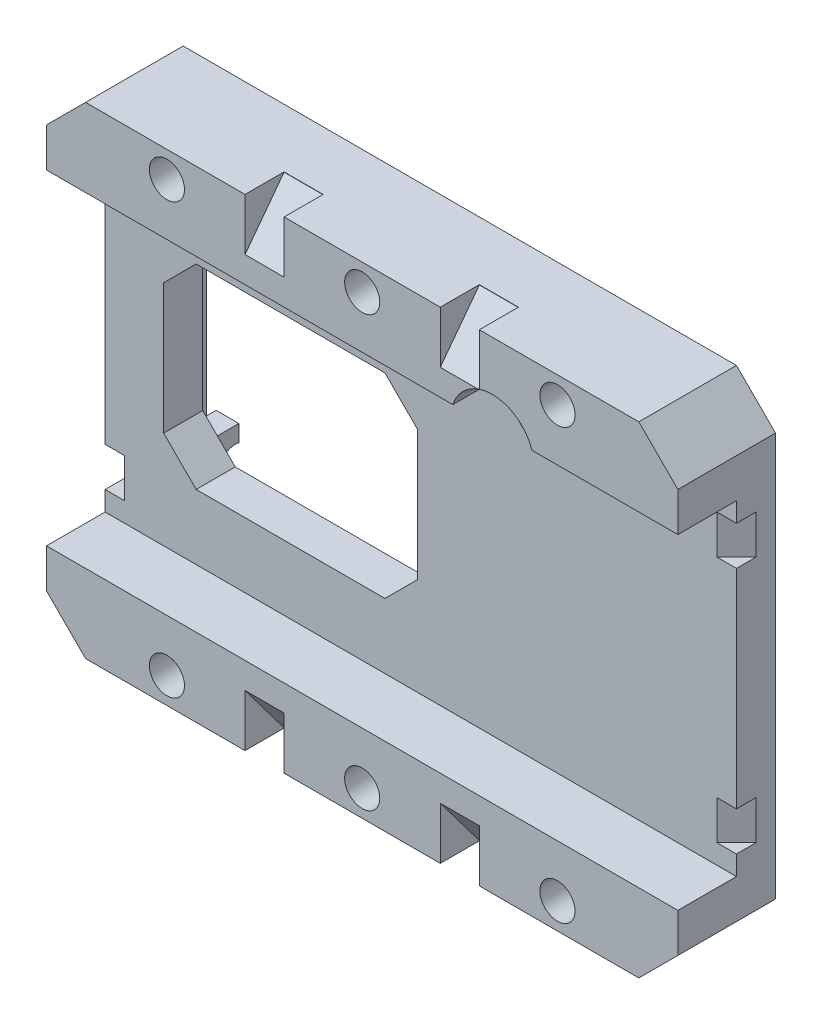
SolidWorks part; units mm, degrees
ref_plane "前视基准面" through (0, 0, 0) normal (0, 0, 1) x (1, 0, 0)
ref_plane "上视基准面" through (0, 0, 0) normal (0, 1, 0) x (1, 0, 0)
ref_plane "右视基准面" through (0, 0, 0) normal (1, 0, 0) x (0, 0, -1)
ref_plane "基准面4" through (0, 0, 5.028) normal (0, 0, -1) x (-1, 0, 0)
sketch "草图1" plane through (0, 0, 5.028) normal (0, 0, -1) x (-1, 0, 0)
  line L0 (-24.25, 18.5) -> (-24.25, -18.5)
  line L1 (-24.25, -18.5) -> (24.25, -18.5)
  line L2 (24.25, -18.5) -> (24.25, 18.5)
  line L3 (24.25, 18.5) -> (-24.25, 18.5)
  line L4 (-24.25, 0) -> (24.25, 0) construction
  line L5 (0, 18.5) -> (0, -18.5) construction
  point P8 (0, 0)
  point P9 (0, 0)
  dimension "D1" = 48.5
  dimension "D2" = 37
extrude "凸台-拉伸1" add sketch "草图1" against normal blind 7.5
sketch "草图2" plane through (24.25, 0, 0) normal (1, 0, 0) x (0, 0, -1)
  line L0 (-12.528, 12.5) -> (-12.528, -12.5)
  line L1 (-12.528, -12.5) -> (-8.028, -12.5)
  line L2 (-8.028, -12.5) -> (-8.028, 12.5)
  line L3 (-8.028, 12.5) -> (-12.528, 12.5)
extrude "切除-拉伸1" cut sketch "草图2" against normal through all
sketch "草图3" plane through (0, 0, 5.028) normal (0, 0, -1) x (-1, 0, 0)
  line L0 (21.75, 13.75) -> (21.75, -13.75)
  line L1 (21.75, -13.75) -> (-19.25, -13.75)
  line L2 (-19.25, -13.75) -> (-19.25, 13.75)
  line L3 (-19.25, 13.75) -> (21.75, 13.75)
  line L4 (-19.25, 0) -> (21.75, 0) construction
  line L5 (24.25, -18.5) -> (24.25, 18.5) construction
  line L6 (-24.25, 18.5) -> (-24.25, -18.5) construction
  point P4 (0, 0)
  point P8 (0, 0)
  point P9 (0, 0)
  dimension "D1" = 27.5
  dimension "D2" = 2.5
  dimension "D3" = 5
extrude "凸台-拉伸2" add sketch "草图3" along normal blind 3.028
sketch "草图4" plane through (0, 0, 2) normal (0, 0, -1) x (-1, 0, 0)
  line L0 (-18.25, -12.5) -> (20, -12.5)
  line L1 (20, -12.5) -> (20, 12.5)
  line L2 (20, 12.5) -> (-18.25, 12.5)
  line L3 (-18.25, 12.5) -> (-18.25, -12.5)
  line L5 (21.75, -13.75) -> (21.75, 13.75) construction
  line L6 (-19.25, 13.75) -> (-19.25, -13.75) construction
  line L7 (-19.25, -13.75) -> (21.75, -13.75) construction
  point P8 (0, 0)
  point P9 (0, 0)
  point P11 (0, 0)
  dimension "D1" = 1
  dimension "D2" = 1.25
  dimension "D3" = 1.75
extrude "切除-拉伸2" cut sketch "草图4" against normal blind 3.028
sketch "草图5" plane through (18.25, 0, 0) normal (-1, 0, 0) x (0, 0, 1)
  line L0 (2, 7.0344) -> (2, -7.0344)
  arc A0 (2, -7.0344) -> (2, 7.0344) centre (-7.722, 0) ccw
extrude "切除-拉伸3" cut sketch "草图5" against normal through all
sketch "草图6" plane through (-21.75, 0, 0) normal (-1, 0, 0) x (0, 0, 1)
  line L0 (2, 7.0344) -> (2, -7.0344)
  arc A0 (2, -7.0344) -> (2, 7.0344) centre (-7.722, 0) ccw
extrude "切除-拉伸4" cut sketch "草图6" against normal through all
sketch "草图7" plane through (0, 0, 8.028) normal (0, 0, 1) x (1, 0, 0)
  line L0 (-7.9784, 7.0292) -> (-13.0216, 7.0292)
  line L1 (-13.0216, -7.0292) -> (-7.9784, -7.0292)
  arc A0 (-1.5, 0) -> (-7.9784, 7.0292) centre (-7.9784, 0.5292) ccw
  arc A1 (-13.0216, 7.0292) -> (-19.5, 0) centre (-13.0216, 0.5292) ccw
  arc A2 (-19.5, 0) -> (-13.0216, -7.0292) centre (-13.0216, -0.5292) ccw
  arc A3 (-7.9784, -7.0292) -> (-1.5, 0) centre (-7.9784, -0.5292) ccw
  point P11 (0, 0)
  dimension "D1" = 19.5
  dimension "D2" = 18
extrude "切除-拉伸5" cut sketch "草图7" against normal through all
ref_plane "基准面5" through (0, 11.5, 0) normal (0, 1, 0) x (1, 0, 0)
sketch "草图8" plane through (0, 11.5, 0) normal (0, 1, 0) x (1, 0, 0)
  line L0 (13, -2.1) -> (10, -2.1)
  line L1 (10, -2.1) -> (10, -12.528)
  line L2 (10, -12.528) -> (13, -12.528)
  line L3 (13, -12.528) -> (13, -2.1)
  line L4 (10, -2.1) -> (10, -12.528) construction
hole_wizard "Ø2.5 (2.5) 直径孔1" positions "草图10" profile "草图9" hole size "Ø2.5" standard "ANSI Metric"
sketch "草图10" plane through (-21.75, 0, 0) normal (-1, 0, 0) x (0, 0, 1)
  point P0 (2.278, 10)
sketch "草图9" plane through (-21.75, 10, 2.278) normal (0, 1, 0) x (0, 0, 1)
  line L0 (0, 0) -> (0, 1.75)
  line L1 (0, 1.75) -> (1.25, 1.75)
  line L2 (1.25, 1.75) -> (1.25, 0)
  line L5 (1.25, 0) -> (0, 0)
  line L11 (0, -6.35) -> (0, 107.95) construction
  dimension "通孔孔直径" = 2.5
  dimension "通孔孔深度" = 1.75
hole_wizard "Ø2.5 (2.5) 直径孔2" positions "草图12" profile "草图11" hole size "Ø2.5" standard "ANSI Metric"
sketch "草图12" plane through (18.25, 0, 0) normal (-1, 0, 0) x (0, 0, 1)
  point P0 (2.278, -10)
  point P1 (2.278, 10)
sketch "草图11" plane through (18.25, -10, 2.278) normal (0, 1, 0) x (0, 0, 1)
  line L0 (0, 0) -> (0, 6)
  line L1 (0, 6) -> (1.25, 6)
  line L2 (1.25, 6) -> (1.25, 0)
  line L5 (1.25, 0) -> (0, 0)
  line L11 (0, -6.35) -> (0, 107.95) construction
  dimension "通孔孔直径" = 2.5
  dimension "通孔孔深度" = 6
hole_wizard "Ø2.5 (2.5) 直径孔3" positions "草图14" profile "草图13" hole size "Ø2.5" standard "ANSI Metric"
sketch "草图14" plane through (-20, 0, 0) normal (1, 0, 0) x (0, 0, -1)
  point P0 (-2.278, -10)
sketch "草图13" plane through (-20, -10, 2.278) normal (0, 1, 0) x (0, 0, -1)
  line L0 (0, 0) -> (0, 4.25)
  line L1 (0, 4.25) -> (1.25, 4.25)
  line L2 (1.25, 4.25) -> (1.25, 0)
  line L5 (1.25, 0) -> (0, 0)
  line L11 (0, -6.35) -> (0, 107.95) construction
  dimension "通孔孔直径" = 2.5
  dimension "通孔孔深度" = 4.25
hole_wizard "Ø2.7 (2.7) 直径孔1" positions "草图16" profile "草图15" hole size "Ø2.7" standard "ANSI Metric" end condition through all
sketch "草图16" plane through (0, 0, 12.528) normal (0, 0, 1) x (1, 0, 0)
  point P0 (0, -16.5)
  point P1 (-15, -16.5)
  point P2 (15, -16.5)
  point P3 (0, 16.5)
  point P4 (-15, 16.5)
  point P5 (15, 16.5)
sketch "草图15" plane through (0, -16.5, 12.528) normal (1, 0, 0) x (0, -1, 0)
  line L0 (0, 0) -> (0, 10.528)
  line L1 (0, 10.528) -> (1.35, 10.528)
  line L2 (1.35, 10.528) -> (1.35, 0)
  line L5 (1.35, 0) -> (0, 0)
  line L11 (0, -6.35) -> (0, 107.95) construction
  dimension "通孔孔直径" = 2.7
  dimension "通孔孔深度" = 10.528
chamfer "倒角1" distance 3 angle 45 4 edges at (24.25, -18.5, 8.778) (24.25, 18.5, 8.778) (-24.25, 18.5, 8.778) (-24.25, -18.5, 8.778)
sketch "草图17" plane through (0, 0, 12.528) normal (0, 0, 1) x (1, 0, 0)
  line L0 (-15, -16.5) -> (0, -16.5) construction
  line L1 (-9, -14.5) -> (-9, -18.5)
  line L2 (-9, -14.5) -> (-6, -14.5)
  line L3 (-9, -18.5) -> (-6, -18.5)
  line L4 (-6, -14.5) -> (-6, -18.5)
  line L5 (-9, -14.5) -> (-6, -18.5) construction
  line L6 (-9, -18.5) -> (-6, -14.5) construction
  line L7 (21.25, -18.5) -> (-21.25, -18.5) construction
  line L8 (0, -5.7904) -> (0, 5.7904) construction
  line L9 (9, -18.5) -> (6, -14.5) construction
  line L10 (9, -14.5) -> (6, -18.5) construction
  line L11 (6, -14.5) -> (6, -18.5)
  line L12 (9, -18.5) -> (6, -18.5)
  line L13 (9, -14.5) -> (6, -14.5)
  line L14 (9, -14.5) -> (9, -18.5)
  line L15 (5.7904, 0) -> (-5.7904, 0) construction
  line L16 (9, 14.5) -> (6, 18.5) construction
  line L17 (9, 18.5) -> (6, 14.5) construction
  line L18 (-9, 18.5) -> (-6, 14.5) construction
  line L19 (-9, 14.5) -> (-6, 18.5) construction
  line L20 (9, 14.5) -> (9, 18.5)
  line L21 (9, 14.5) -> (6, 14.5)
  line L22 (9, 18.5) -> (6, 18.5)
  line L23 (6, 14.5) -> (6, 18.5)
  line L24 (-6, 14.5) -> (-6, 18.5)
  line L25 (-9, 18.5) -> (-6, 18.5)
  line L26 (-9, 14.5) -> (-6, 14.5)
  line L27 (-9, 14.5) -> (-9, 18.5)
  point P4 (-7.5, -16.5)
  point P6 (-7.5, -16.5)
  point P18 (7.5, -16.5)
  point P29 (7.5, 16.5)
  point P30 (-7.5, 16.5)
  dimension "D1" = 3
extrude "切除-拉伸8" cut sketch "草图17" against normal blind 3
chamfer "倒角2" distance 3 angle 53 4 edges at (7.5, -14.5, 9.528) (-7.5, -14.5, 9.528) (-7.5, 14.5, 9.528) (7.5, 14.5, 9.528) first distance on face at (7.5, -14.5, 11.028) first distance on face at (-7.5, -14.5, 11.028) first distance on face at (-7.5, 14.5, 11.028) first distance on face at (7.5, 14.5, 11.028)
sketch "草图19" plane through (0, 0, 8.028) normal (0, 0, 1) x (1, 0, 0)
  line L0 (-24.25, -12.5) -> (-24.25, 12.5) construction
  line L1 (-24.25, -11) -> (-22.25, -11)
  line L2 (-24.25, -11) -> (-24.25, -8)
  line L3 (-24.25, -8) -> (-22.25, -8)
  line L4 (-22.25, -11) -> (-22.25, -8)
  line L6 (5.7904, 0) -> (-5.7904, 0) construction
  line L7 (-22.25, 11) -> (-22.25, 8)
  line L8 (-24.25, 8) -> (-22.25, 8)
  line L9 (-24.25, 11) -> (-24.25, 8)
  line L10 (-24.25, 11) -> (-22.25, 11)
  line L11 (-24.25, -14) -> (24.25, -14) construction
  line L12 (-24.25, -15.5) -> (-24.25, -12.5) construction
  line L13 (24.25, -12.5) -> (24.25, -15.5) construction
  line L14 (0, -14) -> (0, 21.3882) construction
  line L15 (24.25, 11) -> (22.25, 11)
  line L16 (24.25, 11) -> (24.25, 8)
  line L17 (24.25, 8) -> (22.25, 8)
  line L18 (22.25, 11) -> (22.25, 8)
  line L19 (22.25, -11) -> (22.25, -8)
  line L20 (24.25, -8) -> (22.25, -8)
  line L21 (24.25, -11) -> (24.25, -8)
  line L22 (24.25, -11) -> (22.25, -11)
  dimension "D1" = 3
  dimension "D2" = 2
  dimension "D3" = 8
extrude "切除-拉伸9" cut sketch "草图19" against normal blind 1.5
chamfer "倒角3" distance 2 angle 45 4 edges at (22.25, 9.5, 6.528) (22.25, -9.5, 6.528) (-22.25, 9.5, 6.528) (-22.25, -9.5, 6.528)
chamfer "倒角4" distance 1 angle 45 4 edges at (19.25, 13.75, 3.514) (19.25, -13.75, 3.514) (-21.75, -13.75, 3.514) (-21.75, 13.75, 3.514)
sketch "草图20" plane through (0, 0, 2) normal (0, 0, -1) x (-1, 0, 0)
  line L0 (-10, 11.5) -> (-13, 11.5) construction
  circle A0 centre (-10, 11.5) radius 3.2
extrude "切除-拉伸10" cut sketch "草图20" against normal blind 21.5
sketch "草图21" plane through (0, 0, 8.028) normal (0, 0, 1) x (1, 0, 0)
  line L1 (-19.75, -7.5) -> (-0.25, -7.5)
  line L2 (-19.75, -7.5) -> (-19.75, 7.5)
  line L3 (-19.75, 7.5) -> (-0.25, 7.5)
  line L4 (-0.25, -7.5) -> (-0.25, 7.5)
  line L5 (-19.75, -7.5) -> (-0.25, 7.5) construction
  line L6 (-19.75, 7.5) -> (-0.25, -7.5) construction
  point P0 (-10, 0)
  dimension "D1" = 10
  dimension "D2" = 19.5
  dimension "D3" = 15
extrude "切除-拉伸11" cut sketch "草图21" against normal blind 21.5
chamfer "倒角5" distance 2.5 angle 45 4 edges at (-0.25, -7.5, 6.528) (-0.25, 7.5, 6.528) (-19.75, -7.5, 6.528) (-19.75, 7.5, 6.528)
sketch "草图22" plane through (19.25, 0, 0) normal (1, 0, 0) x (0, 0, -1)
  line L1 (4.5, -7.5) -> (-4.5, -7.5)
  line L2 (4.5, -7.5) -> (4.5, 7.5)
  line L3 (4.5, 7.5) -> (-4.5, 7.5)
  line L4 (-4.5, -7.5) -> (-4.5, 7.5)
  line L5 (4.5, -7.5) -> (-4.5, 7.5) construction
  line L6 (4.5, 7.5) -> (-4.5, -7.5) construction
  point P0 (0, 0)
  dimension "D1" = 9
  dimension "D2" = 15
extrude "切除-拉伸12" cut sketch "草图22" against normal blind 51.5
